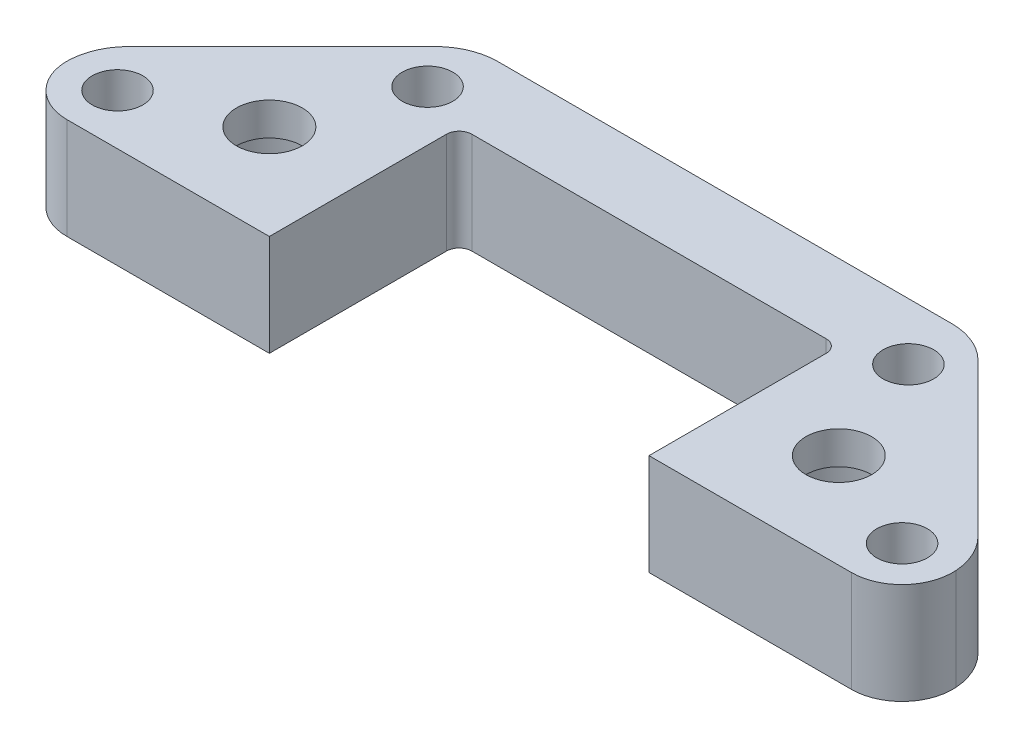
SolidWorks part; units mm, degrees
ref_plane "Plan de face" through (0, 0, 0) normal (0, 0, 1) x (1, 0, 0)
ref_plane "Plan de dessus" through (0, 0, 0) normal (0, 1, 0) x (1, 0, 0)
ref_plane "Plan de droite" through (0, 0, 0) normal (1, 0, 0) x (0, 0, -1)
sketch "Esquisse1" plane through (0, 0, 0) normal (0, 1, 0) x (1, 0, 0)
  line L0 (-30, 15) -> (-15, 0) construction
  line L1 (-30, 0) -> (-15, 0) construction
  line L2 (-30, 0) -> (-30, 15) construction
  line L3 (-30, 15) -> (-15, 15) construction
  line L4 (-15, 0) -> (-15, 15) construction
  line L5 (15, 0) -> (30, 0) construction
  line L6 (15, 0) -> (15, 15) construction
  line L7 (15, 15) -> (30, 15) construction
  line L8 (30, 0) -> (30, 15) construction
  line L9 (15, 0) -> (30, 15) construction
  line L10 (-15, 0) -> (15, 0) construction
  line L11 (-20, 21) -> (20, 21)
  line L12 (-14, 15) -> (14, 15)
  line L13 (0, 21) -> (0, 0) construction
  line L20 (-14, 15) -> (-15, 14)
  line L21 (-15, 14) -> (-15, 0)
  line L22 (14, 15) -> (15, 14)
  line L23 (15, 14) -> (15, 0)
  line L24 (-15, 14) -> (15, 14) construction
  line L29 (-15, 0) -> (-35, 0)
  line L30 (15, 0) -> (35, 0)
  line L31 (-20, 21) -> (-35, 6)
  line L32 (-35, 6) -> (-35, 0)
  line L33 (20, 21) -> (35, 6)
  line L34 (35, 6) -> (35, 0)
  circle A0 centre (-22.5, 7.5) radius 7.5 construction
  circle A1 centre (22.5, 7.5) radius 7.5 construction
  circle A2 centre (-22.5, 7.5) radius 2.6
  circle A3 centre (22.5, 7.5) radius 2.6
  point P8 (0, 0)
  point P21 (0, 15)
  dimension "D3" = 5.2
  dimension "D1" = 30
  dimension "D2" = 15
  dimension "D4" = 6
  dimension "D5" = 1
  dimension "D6" = 28
  dimension "D7" = 20
  dimension "D8" = 6
  dimension "D9" = 40
extrude "Boss.-Extru.1" add sketch "Esquisse1" along normal blind 8
sketch "Esquisse7" plane through (0, 0, 0) normal (0, -1, 0) x (1, 0, 0)
  line L0 (0, -21) -> (0, 12.4029) construction
  line L1 (20, -21) -> (-20, -21) construction
  circle A0 centre (22.5, -7.5) radius 5.1
  circle A1 centre (-22.5, -7.5) radius 5.1
  dimension "D1" = 10.2
extrude "Enlèv. mat.-Extru.4" cut sketch "Esquisse7" against normal blind 5.4
sketch "Esquisse4" plane through (0, 0, 0) normal (0, -1, 0) x (1, 0, 0)
  line L0 (19, -16.5) -> (-19, -16.5) construction
  line L1 (0, -16.5) -> (0, 0) construction
  line L2 (31, -4) -> (-31, -4) construction
  circle A0 centre (19, -16.5) radius 2
  circle A1 centre (-19, -16.5) radius 2
  circle A2 centre (-31, -4) radius 2
  circle A3 centre (31, -4) radius 2
  point P10 (0, -4)
  point P12 (-27.577, -2.1547)
  point P13 (-29.3496, -3.1476)
  dimension "D3" = 4
  dimension "D4" = 62
  dimension "D1" = 16.5
  dimension "D2" = 38
  dimension "D5" = 4
extrude "Enlèv. mat.-Extru.2" cut sketch "Esquisse4" against normal up to surface (8 mm away) up to face at (-22.5, 8, -4.9)
sketch "Esquisse5" plane through (0, 8, 0) normal (0, 1, 0) x (1, 0, 0)
  line L0 (15, 14) -> (14, 14)
  line L1 (14, 14) -> (14, 15)
  line L2 (0, 0) -> (0, 21) construction
  line L3 (-30.9975, 0) -> (30.9975, 0) construction
  line L4 (20, 21) -> (-20, 21) construction
  line L5 (-14, 14) -> (-14, 15)
  line L6 (-15, 14) -> (-14, 14)
  arc A0 (15, 14) -> (14, 15) centre (14, 14) ccw
  arc A1 (-15, 14) -> (-14, 15) centre (-14, 14) cw
extrude "Enlèv. mat.-Extru.3" cut sketch "Esquisse5" against normal through all
fillet "Congé1" radius 5 4 edges at (35, 4, -6) (20, 4, -21) (-35, 4, -6) (-20, 4, -21)
fillet "Congé2" radius 4 2 edges at (35, 4, 0) (-35, 4, 0)
